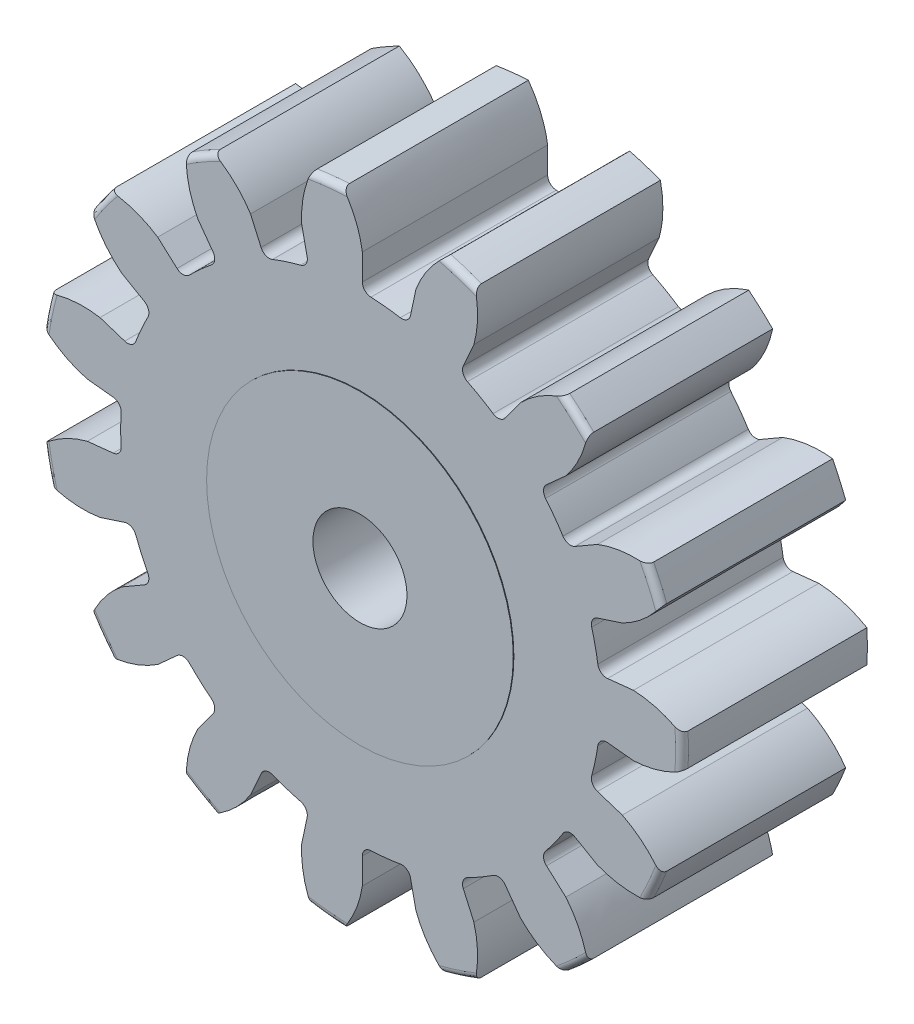
SolidWorks part; units mm, degrees
ref_plane "Front" through (0, 0, 0) normal (0, 0, 1) x (1, 0, 0)
ref_plane "Top" through (0, 0, 0) normal (0, 1, 0) x (1, 0, 0)
ref_plane "Right" through (0, 0, 0) normal (1, 0, 0) x (0, 0, -1)
sketch "Sketch1" plane through (0, 0, 0) normal (0, 0, 1) x (1, 0, 0)
  line L0 (-190.5, 0) -> (190.5, 0) construction
  circle A0 centre (0, 0) radius 10.795
  circle A1 centre (0, 0) radius 9.525 construction
  circle A3 centre (0, 0) radius 8.0556 construction
  dimension "D1" = 1.4694
  dimension "D2" = 2.7394
  dimension "D3" = 1.27
extrude "Boss-Extrude1" add sketch "Sketch1" against normal blind 9.525
sketch "Sketch2" plane through (0, 0, 0) normal (1, 0, 0) x (0, 0, -1)
  line L0 (9.525, 0) -> (19.05, 0)
  line L1 (9.525, 0) -> (9.525, 7.7391)
  line L2 (9.525, 7.7391) -> (19.05, 7.7391)
  line L3 (19.05, 7.7391) -> (19.05, 0)
  point P5 (19.05, -7.7391)
  point P6 (0, -10.795)
  point P7 (9.525, -10.795)
  point P9 (0, 10.795)
revolve "Revolve1" add sketch "Sketch2" angle 360 mid plane about L0
fillet "Fillet2" radius 0.2159 3 edges at (10.795, 0, -9.525) (10.795, 0, 0) (7.7391, 0, -9.525)
sketch "Sketch3" plane through (0, 0, 0) normal (0, 0, 1) x (1, 0, 0)
  line L0 (0, 0) -> (0, 10.795) construction
  line L1 (-2.3089, 8.9279) -> (0, 9.525)
  line L2 (-9.5921, 9.525) -> (9.5921, 9.525) construction
  line L3 (-9.2865, 7.1233) -> (9.2865, 11.9267) construction
  line L4 (-2.3089, 8.9279) -> (0, 0) construction
  line L5 (-5.7038, 7.246) -> (0, 0) construction
  line L6 (-5.7038, 7.246) -> (-0.8315, 11.0813) construction
  line L7 (-1.61, 9.08) -> (0, 0) construction
  line L8 (-1.61, 9.08) -> (0.0338, 9.3714) construction
  arc A0 (-2.3089, 8.9279) -> (-5.7038, 7.246) centre (0, 0) ccw
  circle A1 centre (0, 0) radius 9.525 construction
  circle A2 centre (0, 0) radius 9.2216 construction
  arc A3 (-2.3089, 8.9279) -> (-1.61, 9.08) centre (0, 0) cw
  circle A4 centre (0, 0) radius 10.795 construction
  point P6 (0, 9.525)
  dimension "D1" = 2.3849
  dimension "D3" = 6.2007
  dimension "D5" = 1.6694
  dimension "D2" = 3.8158
  dimension "D4" = 0.7155
sketch "Sketch4" plane through (0, 0, 0) normal (0, 0, 1) x (1, 0, 0)
  line L0 (0, 0) -> (0.9902, 9.4209) construction
  line L1 (0.0599, 9.2214) -> (0.0599, 8.0554)
  line L2 (0, 9.525) -> (1.9804, 9.3169) construction
  line L3 (1.8586, 9.0324) -> (1.6162, 7.8918)
  line L4 (0.0599, 8.0554) -> (0, 0) construction
  line L5 (0, 0) -> (0, 10.795) construction
  line L6 (-5.7038, 7.246) -> (-0.8315, 11.0813) construction
  line L7 (-5.7038, 7.246) -> (-0.8315, 11.0813) construction
  arc A0 (1.6162, 7.8918) -> (0.0599, 8.0554) centre (0, 0) ccw
  arc A1 (0, 9.525) -> (1.9804, 9.3169) centre (0, 0) cw construction
  circle A2 centre (0, 0) radius 9.525 construction
  circle A3 centre (0, 0) radius 9.2216 construction
  circle A4 centre (0, 0) radius 8.0556 construction
  arc A5 (3.1173, 10.6663) -> (-0.8315, 11.0813) centre (0, 0) ccw
  spline S0 degree 2 poles (-0.8315, 11.0813) (-0.0963, 10.2474) (0.0599, 9.2214) knots 0 0 0 1 1 1
  spline S1 degree 2 poles (3.1173, 10.6663) (2.2248, 10.0035) (1.8586, 9.0324) knots 0 0 0 1 1 1
  dimension "D1" = 1.9949
extrude "Cut-Extrude1" cut sketch "Sketch4" against normal through all
fillet "Fillet1" radius 0.2992 2 edges at (1.6162, 7.8918, -4.7625) (0.0599, 8.0554, -4.7625)
pattern_circular "CirPattern1" count 15 over 360 about axis through (0, 0, -9.525) along (0, 0, 1) of "Cut-Extrude1", "Fillet1"
sketch "Sketch5" plane through (0, 0, 0) normal (0, 0, 1) x (1, 0, 0)
  circle A0 centre (0, 0) radius 4.7625
  circle A1 centre (0, 0) radius 4.7625 construction
  dimension "Bore Min" = 9.525
  dimension "Bore Max" = 9.525
extrude "Cut-Extrude2" cut sketch "Sketch5" against normal through all
chamfer "Chamfer1" distance 0.387 angle 45 3 edges at (7.7391, 0, -19.05) (4.7625, 0, 0) (4.7625, 0, -19.05)
sketch "Pitch Dia" plane through (0, 0, 0) normal (0, 0, 1) x (1, 0, 0)
  circle A0 centre (0, 0) radius 9.525 construction
  circle A1 centre (0, 0) radius 9.525
sketch "Sketch6" plane through (0, 0, -19.05) normal (0, 0, -1) x (-1, 0, 0)
  circle A1 centre (0, 0) radius 12.7
  dimension "D1" = 25.4
extrude "Cut-Extrude3" cut sketch "Sketch6" against normal blind 12.827
sketch "Sketch7" plane through (0, 0, -6.223) normal (0, 0, -1) x (-1, 0, 0)
  circle A0 centre (0, 0) radius 5.1495
  circle A1 centre (0, 0) radius 1.5786
  dimension "D1" = 10.2989
  dimension "D2" = 3.1572
extrude "Boss-Extrude2" add sketch "Sketch7" against normal through all contours A0 A1
equation "\"D1@Boss-Extrude1\" = \"Face Wd@Sketch2\""
equation "\"D2@Sketch3\" = \"D1@Sketch3\"*1.6"
equation "\"D3@Sketch3\" = \"D1@Sketch3\"+\"D2@Sketch3\""
equation "\"D4@Sketch3\" = \"D1@Sketch3\"*.3"
equation "\"D5@Sketch3\" = \"D1@Sketch3\"-\"D4@Sketch3\""
equation "\"D1@Sketch4\" = 1.5708/(\"Number of Teeth@Sketch1\"/\"Ptich Dia@Sketch1\")"
equation "\"D1@Chamfer1\" = \"B Hub Dia@Sketch2\"*.025"
equation "\"D1@CirPattern1\" = \"Number of Teeth@Sketch1\""
equation "\"D1@Fillet1\" = \"D1@Sketch4\"*.15"
equation "\"D1@Fillet2\" = \"OD@Sketch1\"*.01"
equation "\"D1@Sketch1\" = 1.157/(\"Number of Teeth@Sketch1\"/\"Ptich Dia@Sketch1\")"
